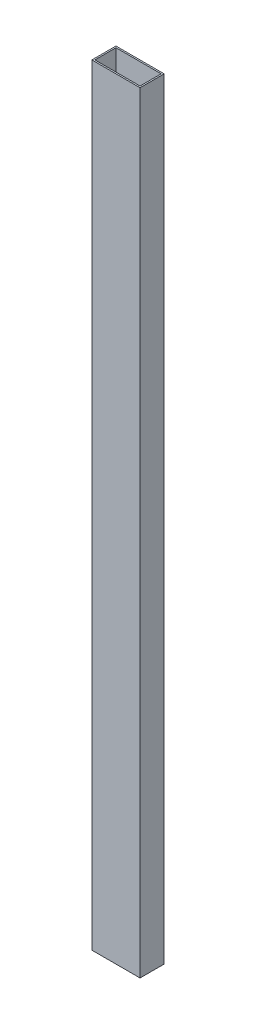
SolidWorks part; units mm, degrees
ref_plane "Front Plane" through (0, 0, 0) normal (0, 0, 1) x (1, 0, 0)
ref_plane "Top Plane" through (0, 0, 0) normal (0, 1, 0) x (1, 0, 0)
ref_plane "Right Plane" through (0, 0, 0) normal (1, 0, 0) x (0, 0, -1)
sketch "Sketch1" plane through (0, 0, 0) normal (0, 1, 0) x (1, 0, 0)
  line L0 (-23.8252, 11.1252) -> (-23.8252, 12.7) construction
  line L1 (-25.4, -12.7) -> (25.4, -12.7)
  line L2 (-25.4, -12.7) -> (-25.4, 12.7)
  line L3 (-25.4, 12.7) -> (25.4, 12.7)
  line L4 (25.4, -12.7) -> (25.4, 12.7)
  line L5 (-25.4, -12.7) -> (25.4, 12.7) construction
  line L6 (-25.4, 12.7) -> (25.4, -12.7) construction
  line L7 (-23.8252, -11.1252) -> (23.8252, -11.1252)
  line L8 (-23.8252, -11.1252) -> (-23.8252, 11.1252)
  line L9 (-23.8252, 11.1252) -> (23.8252, 11.1252)
  line L10 (23.8252, -11.1252) -> (23.8252, 11.1252)
  line L11 (-23.8252, -11.1252) -> (23.8252, 11.1252) construction
  line L12 (-23.8252, 11.1252) -> (23.8252, -11.1252) construction
  line L13 (-23.8252, 11.1252) -> (-25.4, 11.1252) construction
  point P0 (0, 0)
  point P6 (0, 0)
  dimension "D1" = 1.5748
  dimension "D2" = 50.8
  dimension "D3" = 25.4
extrude "Boss-Extrude1" add sketch "Sketch1" along normal blind 812.8
